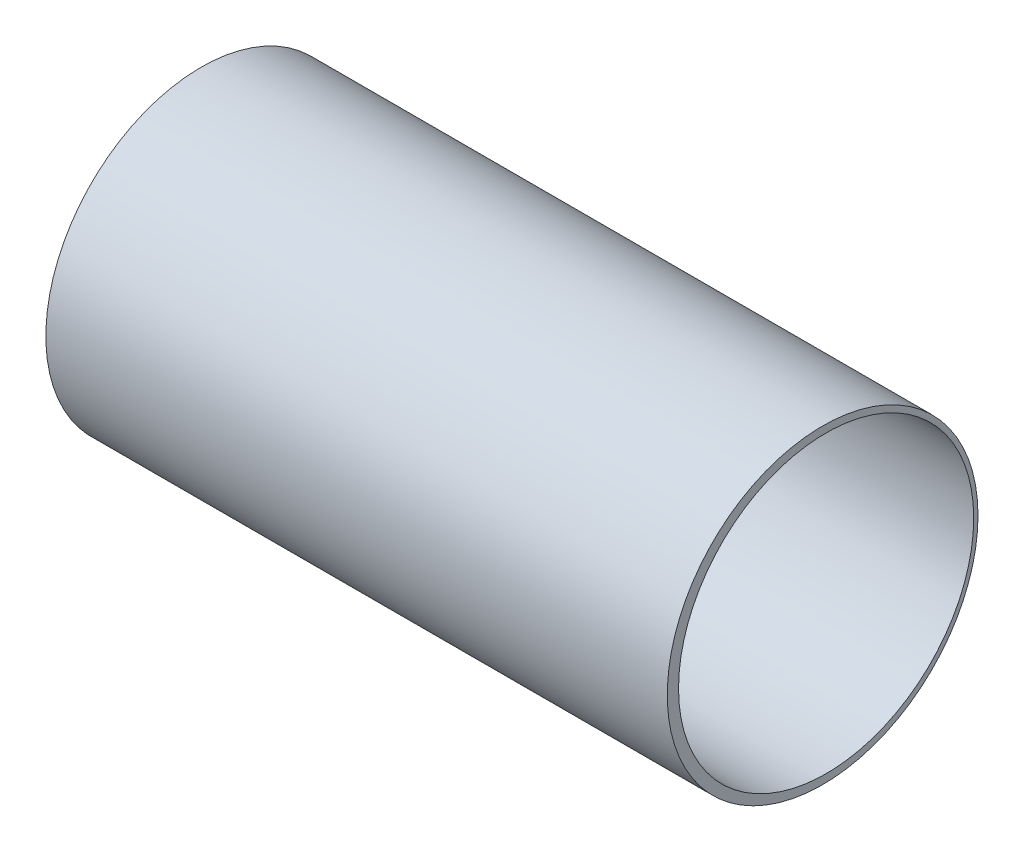
SolidWorks part; units mm, degrees
ref_plane "Front Plane" through (0, 0, 0) normal (0, 0, 1) x (1, 0, 0)
ref_plane "Top Plane" through (0, 0, 0) normal (0, 1, 0) x (1, 0, 0)
ref_plane "Right Plane" through (0, 0, 0) normal (1, 0, 0) x (0, 0, -1)
sketch "Sketch1" plane through (0, 0, 0) normal (1, 0, 0) x (0, 0, -1)
  line L0 (55, 0) -> (-55, 0) construction
  circle A0 centre (0, 0) radius 50
  circle A1 centre (1.1204, 0) radius 47.5
  dimension "D1" = 100
  dimension "D2" = 95
extrude "Boss-Extrude1" add sketch "Sketch1" along normal blind 100 and the other way blind 100
ref_axis "Axis1" through (110, 0, 0) along (-1, 0, 0)
